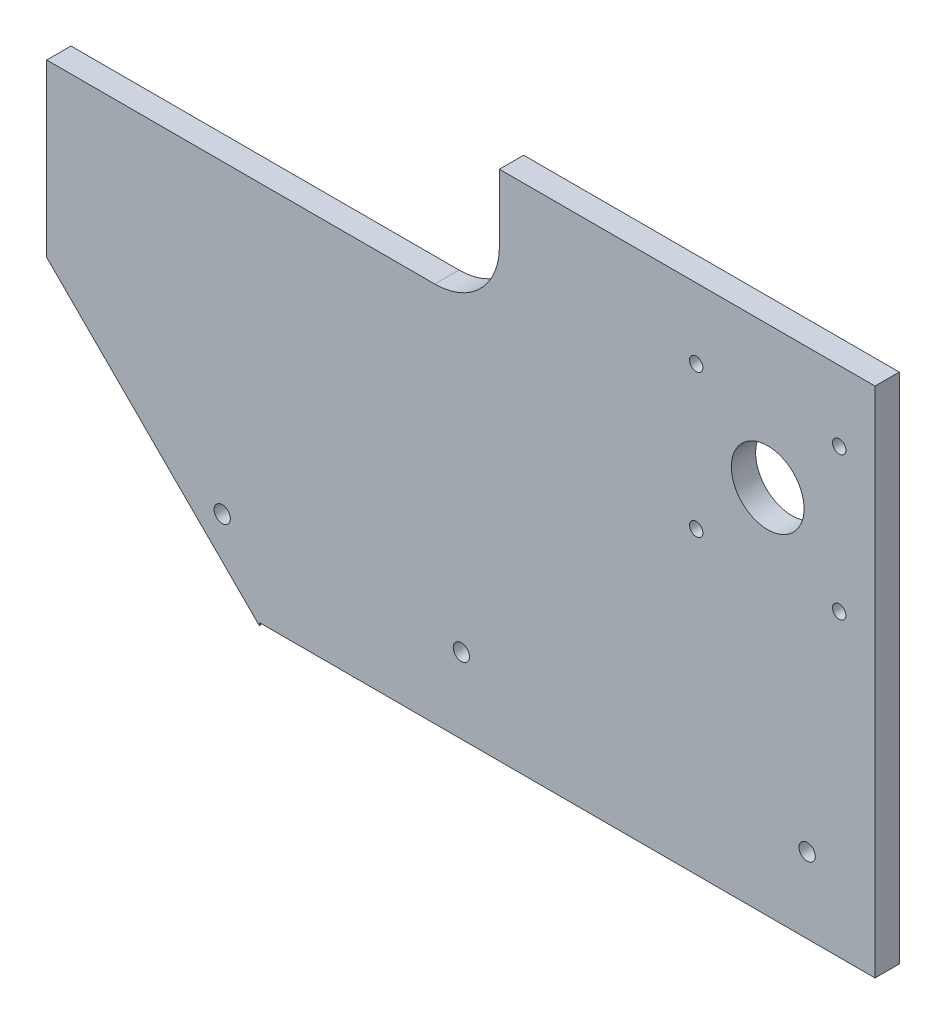
SolidWorks part; units mm, degrees
ref_plane "Front Plane" through (0, 0, 0) normal (0, 0, 1) x (1, 0, 0)
ref_plane "Top Plane" through (0, 0, 0) normal (0, 1, 0) x (1, 0, 0)
ref_plane "Right Plane" through (0, 0, 0) normal (1, 0, 0) x (0, 0, -1)
sketch "Sketch1" plane through (0, 0, 0) normal (0, 0, 1) x (1, 0, 0)
  line L0 (-138.2594, 48.9915) -> (32.2106, -121.4785)
  line L1 (32.2106, -121.4785) -> (222.7106, -121.4785)
  line L2 (-138.2594, 149.5088) -> (-138.2594, 48.9915)
  line L3 (-138.2594, 149.5088) -> (222.7106, 149.5088)
  line L4 (222.7106, -121.4785) -> (222.7106, 149.5088)
  circle A0 centre (180.538, 76.832) radius 14.2875
  circle A2 centre (180.538, 76.832) radius 69.85 construction
  circle A3 centre (180.538, 76.832) radius 318.7974 construction
  point P0 (0, 0)
  point P2 (180.538, 76.832)
  dimension "D4" = 198.3105
  dimension "D1" = 45
  dimension "D2" = 270.9874
  dimension "D5" = 245.11
extrude "Boss-Extrude1" add sketch "Sketch1" along normal blind 9.525
sketch "Sketch2" plane through (0, 0, 9.525) normal (0, 0, 1) x (1, 0, 0)
  line L0 (32.2106, -121.4785) -> (222.7106, -121.4785) construction
  line L1 (241.7606, -121.4785) -> (-19.2702, -121.4785)
  line L2 (241.7606, -121.4785) -> (241.7606, -68.9315)
  line L3 (241.7606, -68.9315) -> (-19.2702, -68.9315)
  line L4 (-19.2702, -121.4785) -> (-19.2702, -68.9315)
extrude "Cut-Extrude1" cut sketch "Sketch2" against normal through all contours L3 L4 L1 L2
sketch "Sketch4" plane through (0, 0, 9.525) normal (0, 0, 1) x (1, 0, 0)
  line L1 (-138.2594, 149.5088) -> (-138.2594, 48.9915) construction
  line L3 (-138.2594, 149.5088) -> (75.1006, 149.5088)
  line L4 (-138.2594, 149.5088) -> (-138.2594, 80.7415)
  line L5 (-138.2594, 80.7415) -> (75.1006, 80.7415)
  line L6 (75.1006, 149.5088) -> (75.1006, 80.7415)
extrude "Cut-Extrude2" cut sketch "Sketch4" against normal through all contours L5 L6 L3 L4
fillet "Fillet2" radius 25.4 2 edges at (-138.2594, 80.7415, 4.7625) (75.1006, 80.7415, 4.7625)
sketch "Sketch16" plane through (222.7106, 0, 0) normal (1, 0, 0) x (0, 0, -1)
  line L0 (0, -68.9315) -> (0, 149.5088) construction
  line L1 (-9.525, 149.5088) -> (0, 149.5088)
  line L2 (-9.525, 149.5088) -> (-9.525, 145.2215)
  line L3 (-9.525, 145.2215) -> (0, 145.2215)
  line L4 (0, 149.5088) -> (0, 145.2215)
extrude "Cut-Extrude3" cut sketch "Sketch16" against normal through all
sketch "Sketch17" plane through (0, 0, 0) normal (0, 0, -1) x (-1, 0, 0)
  line L0 (-222.7106, -68.9315) -> (-222.7106, 145.2215) construction
  line L1 (-75.1006, 145.2215) -> (-222.7106, 145.2215)
  line L2 (-75.1006, 145.2215) -> (-75.1006, 132.5215)
  line L3 (-75.1006, 132.5215) -> (-222.7106, 132.5215)
  line L4 (-222.7106, 145.2215) -> (-222.7106, 132.5215)
  dimension "D1" = 12.7
extrude "Cut-Extrude4" cut sketch "Sketch17" against normal through all
hole_wizard "Tap Drill for M6x0.75 Tap1" positions "Sketch19" profile "Sketch18" hole size "M6x0.75" standard "Lanco STD" end condition through all
sketch "Sketch19" plane through (0, 0, 9.525) normal (0, 0, 1) x (1, 0, 0)
  point P0 (208.638, 104.932)
  point P3 (152.438, 104.932)
  point P6 (152.438, 48.732)
  point P9 (208.638, 48.732)
sketch "Sketch18" plane through (208.638, 104.932, 9.525) normal (1, 0, 0) x (0, -1, 0)
  line L0 (0, 0) -> (0, 9.525)
  line L1 (0, 9.525) -> (2.625, 9.525)
  line L2 (2.625, 9.525) -> (2.625, 0)
  line L5 (2.625, 0) -> (0, 0)
  line L11 (0, -6.35) -> (0, 107.95) construction
  dimension "Thru Hole Dia." = 5.25
  dimension "Thru Hole Depth" = 9.525
hole_wizard "Ø6.4 (6.4) Diameter Hole1" positions "Sketch21" profile "Sketch20" hole size "Ø6.4" standard "ANSI Metric" end condition through all
sketch "Sketch21" plane through (0, 0, 9.525) normal (0, 0, 1) x (1, 0, 0)
  point P0 (196.0406, -39.3145)
  point P2 (60.1506, -39.3145)
  point P4 (-33.8294, -39.3145)
sketch "Sketch20" plane through (196.0406, -39.3145, 9.525) normal (1, 0, 0) x (0, -1, 0)
  line L0 (0, 0) -> (0, 9.525)
  line L1 (0, 9.525) -> (3.2, 9.525)
  line L2 (3.2, 9.525) -> (3.2, 0)
  line L5 (3.2, 0) -> (0, 0)
  line L11 (0, -6.35) -> (0, 107.95) construction
  dimension "Thru Hole Dia." = 6.4
  dimension "Thru Hole Depth" = 9.525
sketch "Sketch22" plane through (0, 0, 9.525) normal (0, 0, 1) x (1, 0, 0)
  line L0 (-102.7904, 145.0855) -> (-102.7904, -100.3395)
  line L1 (222.7106, -68.9315) -> (222.7106, 132.5215) construction
  line L2 (-102.7904, 145.0855) -> (-209.6758, 145.0855)
  line L3 (-209.6758, 145.0855) -> (-209.6758, -95.574)
  line L4 (-209.6758, -95.574) -> (-102.7904, -100.3395)
  dimension "D1" = 325.501
extrude "Cut-Extrude5" cut sketch "Sketch22" against normal through all
